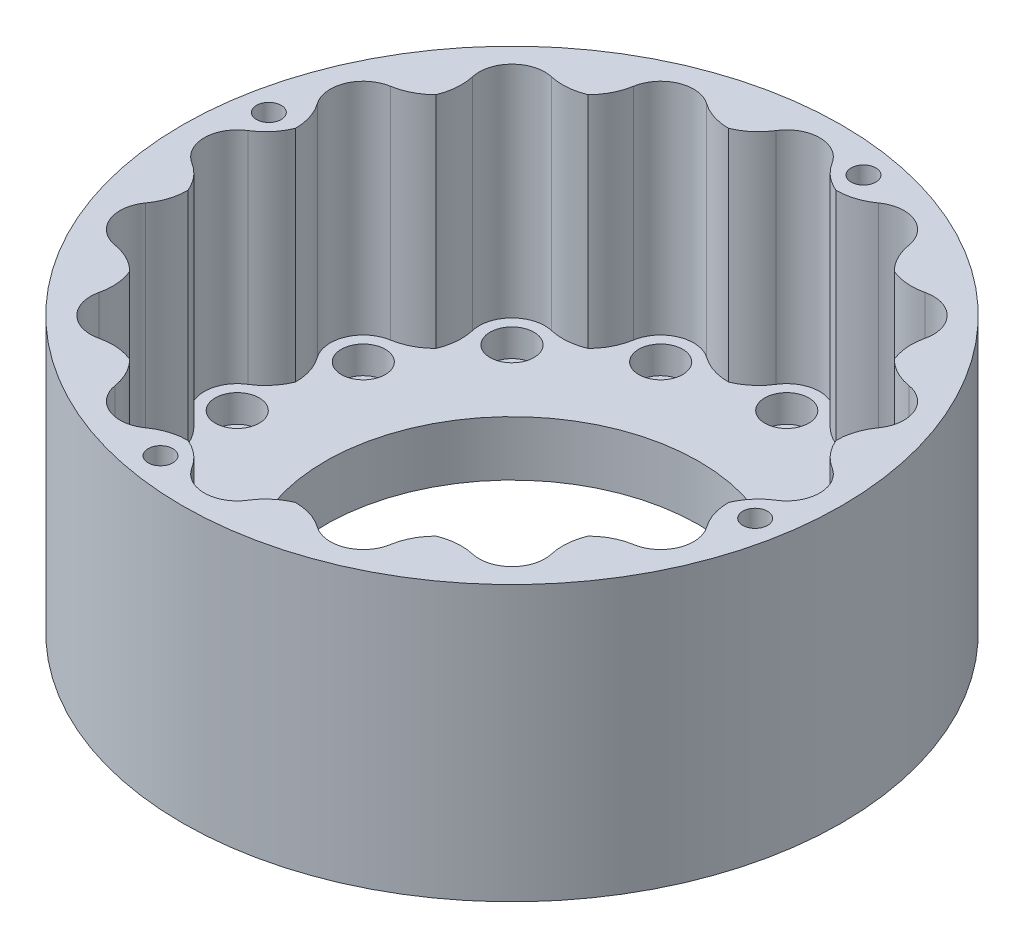
SolidWorks part; units mm, degrees
ref_plane "Front Plane" through (0, 0, 0) normal (0, 0, 1) x (1, 0, 0)
ref_plane "Top Plane" through (0, 0, 0) normal (0, 1, 0) x (1, 0, 0)
ref_plane "Right Plane" through (0, 0, 0) normal (1, 0, 0) x (0, 0, -1)
sketch "Sketch1" plane through (0, 0, 0) normal (0, 1, 0) x (1, 0, 0)
  arc A0 (-50.0283, 13.4631) -> (-51.515, 5.9892) centre (-1.875, 0) ccw
  arc A1 (4.1142, 49.64) -> (-7.8642, 49.64) centre (-1.875, 50) ccw
  arc A2 (-16.6515, 42.0695) -> (-16.6233, 42.0995) centre (-21.0092, 46.194) ccw
  arc A3 (-32.7408, 39.3358) -> (-41.2108, 30.8658) centre (-37.2303, 35.3553) ccw
  arc A4 (-45.4444, 24.5297) -> (-50.0283, 13.4631) centre (-48.069, 19.1342) ccw
  arc A5 (-51.515, 5.9892) -> (-51.515, -5.9892) centre (-51.875, 0) ccw
  arc A6 (-50.0283, -13.4631) -> (-45.4444, -24.5297) centre (-48.069, -19.1342) ccw
  arc A7 (-41.2108, -30.8658) -> (-32.7408, -39.3358) centre (-37.2303, -35.3553) ccw
  arc A8 (-26.4047, -43.5694) -> (-15.3381, -48.1533) centre (-21.0092, -46.194) ccw
  arc A9 (-7.8642, -49.64) -> (4.1142, -49.64) centre (-1.875, -50) ccw
  arc A10 (11.5881, -48.1533) -> (22.6547, -43.5694) centre (17.2592, -46.194) ccw
  arc A11 (28.9908, -39.3358) -> (37.4608, -30.8658) centre (33.4803, -35.3553) ccw
  arc A12 (40.4731, -14.5288) -> (40.4074, -14.5845) centre (44.319, -19.1342) ccw
  arc A13 (47.765, -5.9892) -> (47.765, 5.9892) centre (48.125, 0) ccw
  arc A14 (40.4074, 14.5845) -> (40.4731, 14.5288) centre (44.319, 19.1342) ccw
  arc A15 (37.4608, 30.8658) -> (28.9908, 39.3358) centre (33.4803, 35.3553) ccw
  arc A16 (22.6547, 43.5694) -> (11.5881, 48.1533) centre (17.2592, 46.194) ccw
  circle A17 centre (-1.875, 0) radius 60
  arc A18 (-41.2108, 30.8658) -> (-45.4444, 24.5297) centre (-1.875, 0) ccw
  arc A19 (-26.4047, 43.5694) -> (-32.7408, 39.3358) centre (-1.875, 0) ccw
  arc A20 (-15.3381, 48.1533) -> (-26.4047, 43.5694) centre (-21.0092, 46.194) ccw
  arc A21 (-7.8642, 49.64) -> (-15.3381, 48.1533) centre (-1.875, 0) ccw
  arc A22 (11.5881, 48.1533) -> (4.1142, 49.64) centre (-1.875, 0) ccw
  arc A23 (28.9908, 39.3358) -> (22.6547, 43.5694) centre (-1.875, 0) ccw
  arc A24 (41.6944, 24.5297) -> (37.4608, 30.8658) centre (-1.875, 0) ccw
  arc A25 (46.2783, 13.4631) -> (41.6944, 24.5297) centre (44.319, 19.1342) ccw
  arc A26 (46.2783, -13.4631) -> (47.765, -5.9892) centre (-1.875, 0) ccw
  arc A27 (41.6944, -24.5297) -> (46.2783, -13.4631) centre (44.319, -19.1342) ccw
  arc A28 (37.4608, -30.8658) -> (41.6944, -24.5297) centre (-1.875, 0) ccw
  arc A29 (-51.515, -5.9892) -> (-50.0283, -13.4631) centre (-1.875, 0) ccw
  arc A30 (-45.4444, -24.5297) -> (-41.2108, -30.8658) centre (-1.875, 0) ccw
  arc A31 (-32.7408, -39.3358) -> (-26.4047, -43.5694) centre (-1.875, 0) ccw
  arc A32 (-15.3381, -48.1533) -> (-7.8642, -49.64) centre (-1.875, 0) ccw
  arc A33 (-16.6233, -42.0995) -> (-16.6515, -42.0695) centre (-21.0092, -46.194) ccw
  arc A34 (4.1142, -49.64) -> (11.5881, -48.1533) centre (-1.875, 0) ccw
  arc A35 (22.6547, -43.5694) -> (28.9908, -39.3358) centre (-1.875, 0) ccw
  arc A36 (47.765, 5.9892) -> (46.2783, 13.4631) centre (-1.875, 0) ccw
  spline S0 degree 4 poles (44.0747, 11.4987) (44.2543, 11.2167) (44.5698, 10.6242) (44.9021, 9.6808) (45.0642, 8.3642) (44.9446, 7.1282) (44.593, 6.0249) (44.1211, 5.1947) (43.695, 4.5754) (43.3564, 4.0472) (43.0998, 3.6163) (42.8821, 3.198) (42.6994, 2.7973) (42.5503, 2.4153) (42.4301, 2.0557) (42.3415, 1.7357) (42.2778, 1.4587) (42.224, 1.1791) (42.1875, 0.9457) (42.1595, 0.7089) (42.1421, 0.4978) (42.1336, 0.3578) (42.1278, 0.2085) (42.1243, 0.037) (42.1247, -0.0678) (42.1293, -0.2634) (42.1379, -0.4367) (42.15, -0.5999) (42.1691, -0.7936) (42.1974, -1.0101) (42.2414, -1.2799) (42.3074, -1.6012) (42.4037, -1.9716) (42.5387, -2.3877) (42.6983, -2.7948) (42.8796, -3.1931) (43.1366, -3.6835) (43.482, -4.2594) (43.9287, -4.9065) (44.4091, -5.6745) (44.8007, -6.6105) (45.0295, -7.7093) (45.0295, -8.9484) (44.7352, -10.2696) (44.1902, -11.4212) (43.4619, -12.3657) (42.6206, -13.0778) (41.7593, -13.602) (40.7824, -14.2408) (39.77, -15.1062) (38.838, -16.2841) (38.1405, -17.7977) (37.8498, -19.2831) (37.8586, -20.6377) (38.0279, -21.8199) (38.2279, -22.8394) (38.2788, -23.9779) (38.0615, -25.1966) (37.5489, -26.4121) (36.7247, -27.5436) (35.7476, -28.3911) (34.706, -28.96) (33.6586, -29.2738) (32.6702, -29.405) (31.5286, -29.5836) (30.2595, -29.9481) (28.9262, -30.6268) (27.659, -31.7106) (26.7717, -32.9447) (26.2118, -34.1914) (25.9145, -35.2243) (25.7304, -35.9895) (25.5039, -36.7438) (25.1586, -37.555) (24.5413, -38.4785) (23.5696, -39.3957) (22.3328, -40.1097) (21.0527, -40.4927) (19.9443, -40.5655) (19.0691, -40.4589) (18.3026, -40.2779) (17.5479, -40.0547) (16.5047, -39.7958) (15.1451, -39.6573) (13.6327, -39.8087) (12.0605, -40.3642) (10.8061, -41.1795) (9.8558, -42.0964) (9.1304, -42.9957) (8.5226, -43.7861) (7.7271, -44.5363) (6.7136, -45.1539) (5.4911, -45.5763) (4.0991, -45.7244) (2.7902, -45.5605) (1.6261, -45.1394) (0.6656, -44.526) (-0.1173, -43.8431) (-1.0565, -43.1053) (-2.2252, -42.4205) (-3.657, -41.9295) (-5.3166, -41.7767) (-6.8026, -41.9949) (-8.0583, -42.439) (-9.1, -42.9656) (-9.9846, -43.4494) (-11.0219, -43.8219) (-12.2041, -43.9805) (-13.4901, -43.8751) (-14.8122, -43.455) (-15.9301, -42.7928) (-16.8127, -41.9651) (-17.4446, -41.0507) (-17.8788, -40.1387) (-18.4163, -39.084) (-19.1877, -37.9587) (-20.2985, -36.882) (-21.7915, -36.02) (-23.2794, -35.5964) (-24.6396, -35.491) (-25.8217, -35.5529) (-26.8286, -35.6328) (-27.9365, -35.5428) (-29.0946, -35.1922) (-30.227, -34.5552) (-31.2519, -33.6204) (-31.9862, -32.5593) (-32.4399, -31.4562) (-32.636, -30.3717) (-32.6594, -29.3636) (-32.7241, -28.1982) (-32.9674, -26.8887) (-33.5214, -25.4926) (-34.4835, -24.1318) (-35.6246, -23.1374) (-36.8021, -22.4676) (-37.9106, -22.0232) (-38.8934, -21.6866) (-39.9049, -21.1614) (-40.8517, -20.3639) (-41.648, -19.3123) (-42.2158, -18.0327) (-42.4612, -16.7628) (-42.4331, -15.5762) (-42.1811, -14.5123) (-41.8006, -13.5907) (-41.3845, -12.5128) (-41.0655, -11.2314) (-40.9867, -9.7374) (-41.2916, -8.0981) (-41.8623, -6.8333) (-42.485, -5.9251) (-43.0125, -5.3085) (-43.3736, -4.9275) (-43.7476, -4.5595) (-44.1231, -4.193) (-44.4829, -3.8105) (-44.8105, -3.3997) (-45.0744, -2.9955) (-45.2825, -2.6081) (-45.444, -2.2456) (-45.5676, -1.9138) (-45.6577, -1.6174) (-45.7221, -1.3598) (-45.7672, -1.1433) (-45.7981, -0.9691) (-45.8239, -0.7941) (-45.8419, -0.6396) (-45.8542, -0.5087) (-45.8622, -0.3996) (-45.8674, -0.31) (-45.8722, -0.1929) (-45.8754, -0.0484) (-45.8754, 0.057) (-45.8707, 0.2539) (-45.8614, 0.4217) (-45.8475, 0.5867) (-45.8289, 0.7543) (-45.8057, 0.9209) (-45.7778, 1.0866) (-45.7208, 1.3751) (-45.6162, 1.7824) (-45.4517, 2.2512) (-45.2056, 2.7679) (-44.9364, 3.2145) (-44.6596, 3.5954) (-44.3529, 3.9526) (-44.0247, 4.2897) (-43.6878, 4.6178) (-43.3537, 4.9489) (-43.036, 5.2844) (-42.7388, 5.6275) (-42.4647, 5.9787) (-42.2147, 6.3375) (-41.9285, 6.8032) (-41.6301, 7.388) (-41.2988, 8.2445) (-41.0869, 9.2182) (-41.0245, 10.1783) (-41.079, 10.9169) (-41.1306, 11.2832) (-41.1623, 11.4653) knots 0 0 0 0 0 0.00752 0.015039 0.022311 0.029582 0.03522 0.040858 0.043677 0.046496 0.049315 0.052134 0.054265 0.056396 0.058526 0.060657 0.061722 0.062788 0.064918 0.065984 0.067049 0.067582 0.068115 0.06918 0.070492 0.071149 0.071805 0.073033 0.074262 0.07549 0.076719 0.079176 0.081633 0.084089 0.086546 0.089003 0.09146 0.096539 0.101618 0.106697 0.111776 0.11923 0.126684 0.134323 0.141963 0.147625 0.153288 0.15895 0.164612 0.173852 0.183092 0.192408 0.201724 0.207559 0.213395 0.219231 0.225067 0.233024 0.240981 0.24862 0.25626 0.261858 0.267455 0.273053 0.278651 0.287828 0.297005 0.30639 0.315776 0.321674 0.327572 0.330521 0.33347 0.339368 0.347323 0.355277 0.363232 0.371186 0.377084 0.380033 0.382982 0.38888 0.394778 0.404164 0.413549 0.422726 0.431904 0.437501 0.443099 0.448697 0.454294 0.461934 0.469574 0.477531 0.485487 0.491323 0.497159 0.502995 0.508831 0.518146 0.527462 0.536702 0.545942 0.551604 0.557267 0.562929 0.568591 0.576231 0.58387 0.591691 0.599511 0.605182 0.610853 0.616525 0.622196 0.631785 0.641374 0.650964 0.660553 0.666224 0.671895 0.677566 0.683238 0.691058 0.698878 0.706518 0.714157 0.71982 0.725482 0.731145 0.736807 0.746047 0.755287 0.764602 0.773918 0.779754 0.78559 0.791426 0.797261 0.805218 0.813175 0.820815 0.828454 0.834052 0.83965 0.845248 0.850845 0.860022 0.869199 0.878585 0.887971 0.89092 0.893869 0.896818 0.899767 0.902716 0.905665 0.908614 0.911563 0.913551 0.91554 0.917528 0.919517 0.920511 0.921506 0.9225 0.923494 0.924489 0.924986 0.925483 0.92598 0.926477 0.927472 0.928416 0.929361 0.930305 0.931249 0.932194 0.933138 0.934083 0.935027 0.938805 0.942583 0.945226 0.947869 0.950513 0.953156 0.955799 0.958442 0.961086 0.963729 0.966185 0.968641 0.971097 0.973554 0.978466 0.983378 0.991689 0.995845 1 1 1 1 1 construction
  spline S1 degree 4 poles (40.4731, -14.5288) (40.4566, -14.5426) (40.4402, -14.5565) (40.4237, -14.5705) (40.4074, -14.5845) knots 0.165033 0.165033 0.165033 0.165033 0.165033 0.165518 0.165518 0.165518 0.165518 0.165518
  spline S2 degree 4 poles (40.4731, 14.5288) (40.4566, 14.5426) (40.4402, 14.5565) (40.4237, 14.5705) (40.4074, 14.5845) knots 0.165033 0.165033 0.165033 0.165033 0.165033 0.165518 0.165518 0.165518 0.165518 0.165518
  spline S3 degree 4 poles (-16.6233, 42.0995) (-16.6304, 42.0921) (-16.6375, 42.0846) (-16.6445, 42.0771) (-16.6515, 42.0695) knots 0.600544 0.600544 0.600544 0.600544 0.600544 0.600775 0.600775 0.600775 0.600775 0.600775
  dimension "D1" = 16
extrude "Boss-Extrude1" add sketch "Sketch1" along normal blind 50 contours A17 | A26 A13 A36 A25 A24 A15 A23 A16 A22 A1 A21 A20 A19 A3 A18 A4 A0 A5 A29 A6 A30 A7 A31 A8 A32 A9 A34 A10 A35 A11 A28 A27
sketch "Sketch3" plane through (0, 0, 0) normal (0, 1, 0) x (1, 0, 0)
  circle A0 centre (-1.875, 0) radius 60
extrude "Boss-Extrude2" add sketch "Sketch3" along normal blind 10
fillet "Fillet1" radius 10 2 edges at (11.5881, 30, -48.1533) (4.1142, 30, -49.64)
fillet "Fillet2" radius 10 30 edges at (-50.0283, 30, -13.4631) (-51.515, 30, -5.9892) (-51.515, 30, 5.9892) (-50.0283, 30, 13.4631) (-45.4444, 30, 24.5297) (-41.2108, 30, 30.8658) (-32.7408, 30, 39.3358) (-26.4047, 30, 43.5694) (-15.3381, 30, 48.1533) (-7.8642, 30, 49.64) (-45.4444, 30, -24.5297) (-41.2108, 30, -30.8658) (-32.7408, 30, -39.3358) (-26.4047, 30, -43.5694) (-7.8642, 30, -49.64) (-15.3381, 30, -48.1533) (4.1142, 30, 49.64) (11.5881, 30, 48.1533) (22.6547, 30, 43.5694) (28.9908, 30, 39.3358) (37.4608, 30, 30.8658) (41.6944, 30, 24.5297) (46.2783, 30, 13.4631) (47.765, 30, 5.9892) (47.765, 30, -5.9892) (46.2783, 30, -13.4631) (41.6944, 30, -24.5297) (37.4608, 30, -30.8658) (28.9908, 30, -39.3358) (22.6547, 30, -43.5694)
sketch "Sketch5" plane through (0, 50, 0) normal (0, 1, 0) x (1, 0, 0)
  circle A0 centre (-11.7359, -54.1088) radius 2.25
  circle A3 centre (-55.9838, 9.8609) radius 2.25
  circle A4 centre (7.9859, 54.1088) radius 2.25
  circle A5 centre (52.2338, -9.8609) radius 2.25
  point P12 (-1.875, 0)
  dimension "D1" = 4
extrude "Cut-Extrude2" cut sketch "Sketch5" against normal blind 6.1 contours A4 | A3 | A0 | A5 region at (7.9859, 50, -54.1088)
sketch "Sketch6" plane through (0, 10, 0) normal (0, 1, 0) x (1, 0, 0)
  circle A0 centre (-1.875, 0) radius 50 construction
  circle A1 centre (-1.875, 50) radius 4
  circle A2 centre (17.2592, 46.194) radius 4
  circle A3 centre (33.4803, 35.3553) radius 4
  circle A4 centre (44.319, 19.1342) radius 4
  circle A5 centre (48.125, 0) radius 4
  circle A6 centre (44.319, -19.1342) radius 4
  circle A7 centre (33.4803, -35.3553) radius 4
  circle A8 centre (17.2592, -46.194) radius 4
  circle A9 centre (-1.875, -50) radius 4
  circle A10 centre (-21.0092, -46.194) radius 4
  circle A11 centre (-37.2303, -35.3553) radius 4
  circle A12 centre (-48.069, -19.1342) radius 4
  circle A13 centre (-51.875, 0) radius 4
  circle A14 centre (-48.069, 19.1342) radius 4
  circle A15 centre (-37.2303, 35.3553) radius 4
  circle A16 centre (-21.0092, 46.194) radius 4
  dimension "D1" = 16
extrude "Cut-Extrude3" cut sketch "Sketch6" against normal blind 5
sketch "Sketch7" plane through (0, 0, 0) normal (0, -1, 0) x (1, 0, 0)
  circle A1 centre (-1.875, 0) radius 34
  point P0 (-1.875, 0)
  dimension "D1" = 68
extrude "Cut-Extrude4" cut sketch "Sketch7" against normal blind 10
